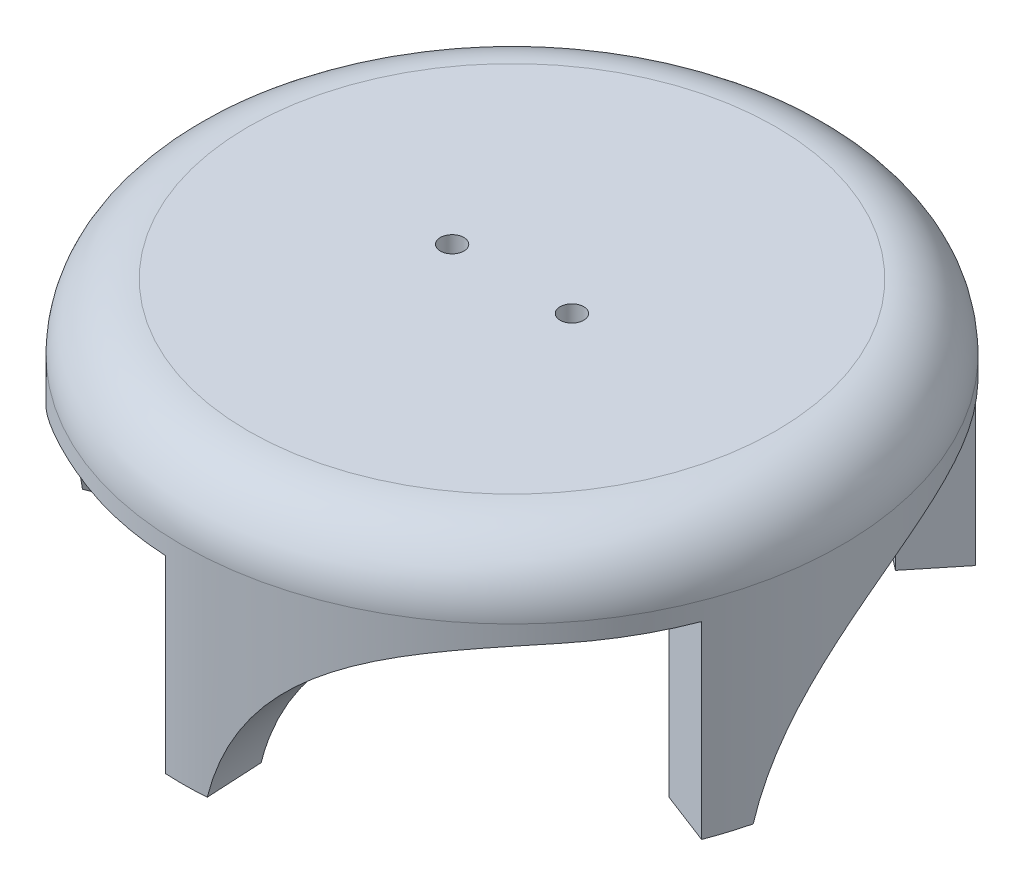
SolidWorks part; units mm, degrees
ref_plane "Front Plane" through (0, 0, 0) normal (0, 0, 1) x (1, 0, 0)
ref_plane "Top Plane" through (0, 0, 0) normal (0, 1, 0) x (1, 0, 0)
ref_plane "Right Plane" through (0, 0, 0) normal (1, 0, 0) x (0, 0, -1)
sketch "Sketch1" plane through (0, 0, 0) normal (0, 1, 0) x (1, 0, 0)
  circle A0 centre (0, 0) radius 13.97
  dimension "D1" = 27.94
extrude "Boss-Extrude1" add sketch "Sketch1" along normal blind 3.556
sketch "Sketch2" plane through (0, 0, 0) normal (0, -1, 0) x (1, 0, 0)
  line L0 (0, -13.97) -> (0, 13.97) construction
  line L1 (-13.97, 0) -> (13.97, 0) construction
  circle A0 centre (0, 0) radius 13.97 construction
  circle A1 centre (2.54, 0) radius 1.0795
  circle A2 centre (-2.54, 0) radius 1.0795
  point P7 (0, 0)
  dimension "D1" = 2.159
  dimension "D2" = 2.54
extrude "Cut-Extrude1" cut sketch "Sketch2" against normal blind 1.127
sketch "Sketch3" plane through (0, 1.127, 0) normal (0, -1, 0) x (1, 0, 0)
  circle A2 centre (-2.54, 0) radius 0.5
  circle A3 centre (2.54, 0) radius 0.5
  dimension "D1" = 1
  dimension "D2" = 1
extrude "Cut-Extrude2" cut sketch "Sketch3" against normal through all
sketch "Sketch4" plane through (0, 0, 0) normal (0, -1, 0) x (1, 0, 0)
  line L0 (0, 0) -> (0, 13.97) construction
  line L1 (0, 0) -> (-0.7311, 13.9509)
  line L2 (0, 0) -> (0.7311, 13.9509)
  line L3 (0, 0) -> (13.0421, 5.0064)
  line L4 (0, 0) -> (13.494, 3.6157)
  line L5 (0, 0) -> (8.7916, -10.8567)
  line L6 (0, 0) -> (7.6086, -11.7162)
  line L7 (0, 0) -> (-7.6086, -11.7162)
  line L8 (0, 0) -> (-8.7916, -10.8567)
  line L9 (0, 0) -> (-13.494, 3.6157)
  line L10 (0, 0) -> (-13.0421, 5.0064)
  circle A0 centre (0, 0) radius 11.557
  circle A1 centre (0, 0) radius 13.97
  point P17 (0, 0)
  dimension "D1" = 23.114
  dimension "D2" = 3
  dimension "D3" = 5
extrude "Boss-Extrude4" add sketch "Sketch4" along normal blind 15.621 contours A0 L10 L5 L9 | A0 L8 L5 L7 | A0 L6 L5 | A0 L4 L5 L3 | L0 A0 L2 L5 | A0 L0 A1 L1 region at (-0.3351, 0, 12.7957) region at (0.3351, 0, 12.7957) region at (12.1694, 0, 3.9541) region at (7.5211, 0, -10.3519) region at (-7.5211, 0, -10.3519) region at (-12.1694, 0, 3.9541)
sketch "Sketch6" plane through (0, -15.621, 0) normal (0, -1, 0) x (1, 0, 0)
  line L0 (0.7311, 13.9509) -> (0.6048, 11.5412)
  line L1 (0.7311, 13.9509) -> (2.4107, 13.8628)
  line L2 (0.6048, 11.5412) -> (2.2844, 11.4531)
  line L3 (2.4107, 13.8628) -> (2.2844, 11.4531)
  line L4 (13.4849, 3.5456) -> (11.1541, 2.9211)
  line L5 (13.4849, 3.5456) -> (13.9202, 1.9211)
  line L6 (13.9202, 1.9211) -> (11.5894, 1.2966)
  line L7 (11.1541, 2.9211) -> (11.5894, 1.2966)
  line L8 (7.5301, -11.7993) -> (6.2158, -9.7756)
  line L9 (7.5301, -11.7993) -> (6.1195, -12.7153)
  line L10 (6.1195, -12.7153) -> (4.8053, -10.6916)
  line L11 (6.2158, -9.7756) -> (4.8053, -10.6916)
  line L12 (-8.904, -10.8778) -> (-7.3854, -9.0025)
  line L13 (-8.904, -10.8778) -> (-10.211, -9.8193)
  line L14 (-10.211, -9.8193) -> (-8.6925, -7.9441)
  line L15 (-7.3854, -9.0025) -> (-8.6925, -7.9441)
  line L16 (-13.1059, 5.0367) -> (-10.8532, 4.172)
  line L17 (-13.1059, 5.0367) -> (-12.5032, 6.6068)
  line L18 (-12.5032, 6.6068) -> (-10.2505, 5.7421)
  line L19 (-10.8532, 4.172) -> (-10.2505, 5.7421)
  circle A0 centre (0, 0) radius 13.97
  circle A1 centre (0, 0) radius 11.557
  point P29 (-0.0528, -0.0288)
  line M7 (-10.7894, 4.1417) -> (-13.0421, 5.0064)
  dimension "D1" = 5
extrude "Boss-Extrude5" add sketch "Sketch6" against normal blind 2.54 contours L3 A0 L0 L2 | L18 A0 L19 M7 | L14 A0 L12 L15 | L10 A0 L8 L11 | L6 A0 L4 L7 region at (1.5009, -15.621, 12.6856) region at (-11.6318, -15.621, 5.3649) region at (12.5308, -15.621, 2.4223) region at (-8.7536, -15.621, -9.3666) region at (6.1551, -15.621, -11.2134)
fillet "Fillet1" radius 10.414 5 edges at (-8.0323, 0, -9.9191) (-11.9158, 0, 4.574) (0.668, 0, 12.746) (12.3286, 0, 3.3034) (6.9515, 0, -10.7044)
fillet "Fillet2" radius 2.794 1 edges at (0, 3.556, 13.97)
sketch "Sketch7" plane through (0, -13.081, 0) normal (0, 1, 0) x (1, 0, 0)
  line L5 (-13.0421, -5.0064) -> (-10.7894, -4.1417)
  line L8 (0.6048, -11.5412) -> (1.9803, -11.4691)
  line L9 (0.6048, -11.5412) -> (2.2844, -11.4531) construction
  line L10 (1.9803, -11.4691) -> (2.103, -13.8108)
  line L11 (0.7311, -13.9509) -> (0.6048, -11.5412)
  line L12 (-10.7894, -4.1417) -> (-10.2958, -5.4275)
  line L13 (-10.2958, -5.4275) -> (-12.485, -6.2679)
  line L14 (-8.7916, 10.8567) -> (-7.2731, 8.9815)
  line L15 (-7.2731, 8.9815) -> (-8.3434, 8.1147)
  line L16 (-8.3434, 8.1147) -> (-9.8192, 9.937)
  line L17 (7.6086, 11.7162) -> (6.2944, 9.6925)
  line L18 (6.2944, 9.6925) -> (5.1393, 10.4427)
  line L19 (5.1393, 10.4427) -> (6.4164, 12.4093)
  line L20 (13.494, -3.6157) -> (11.1632, -2.9912)
  line L21 (11.1632, -2.9912) -> (11.5197, -1.6608)
  line L22 (11.5197, -1.6608) -> (13.7847, -2.2677)
  arc A0 (-12.485, -6.2679) -> (-13.0421, -5.0064) centre (0, 0) cw
  arc A2 (0.7311, -13.9509) -> (2.4053, -13.7614) centre (0, 0) ccw construction
  arc A3 (2.103, -13.8108) -> (0.7311, -13.9509) centre (0, 0) cw
  arc A4 (-9.8192, 9.937) -> (-8.7916, 10.8567) centre (0, 0) cw
  arc A5 (6.4164, 12.4093) -> (7.6086, 11.7162) centre (0, 0) cw
  arc A6 (13.7847, -2.2677) -> (13.494, -3.6157) centre (0, 0) cw
  point P30 (0, 0)
  dimension "D1" = 5
extrude "Cut-Extrude14" cut sketch "Sketch7" against normal blind 1.27
sketch "Sketch8" plane through (0, -15.621, 0) normal (0, -1, 0) x (1, 0, 0)
  circle A2 centre (0, 0) radius 30.1089
extrude "Cut-Extrude16" cut sketch "Sketch8" against normal blind 7.62
